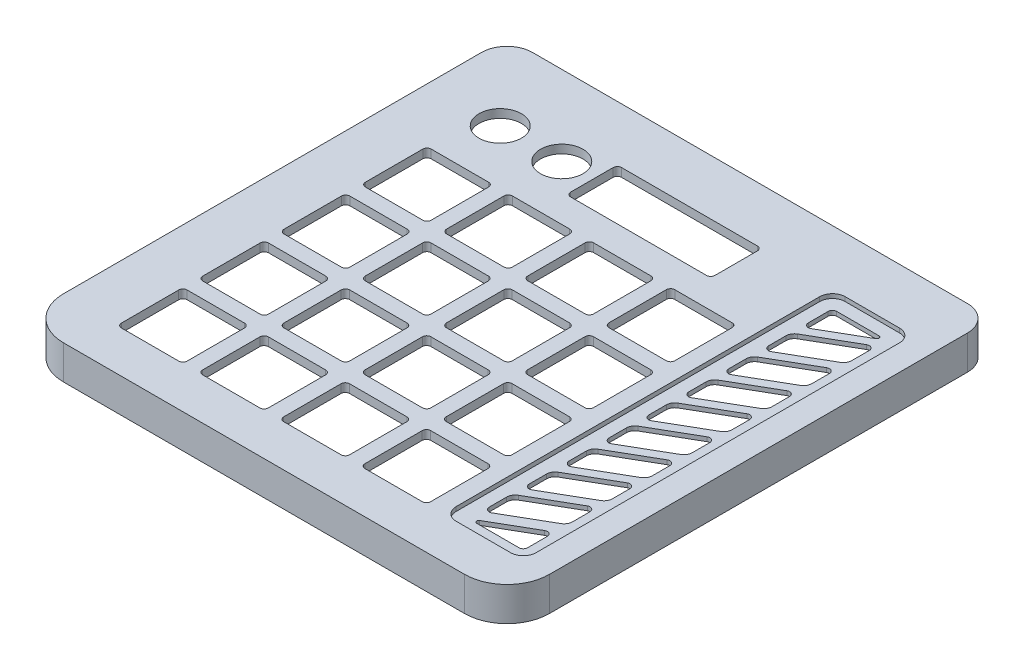
SolidWorks part; units mm, degrees
ref_plane "Plan de face" through (0, 0, 0) normal (0, 0, 1) x (1, 0, 0)
ref_plane "Plan de dessus" through (0, 0, 0) normal (0, 1, 0) x (1, 0, 0)
ref_plane "Plan de droite" through (0, 0, 0) normal (1, 0, 0) x (0, 0, -1)
sketch "Esquisse2" plane through (0, 0, 0) normal (0, 1, 0) x (1, 0, 0)
  line L1 (8, 0) -> (102.5, 0)
  line L2 (0, 8) -> (0, 106.5)
  line L3 (4, 110.5) -> (106.5, 110.5)
  line L4 (110.5, 8) -> (110.5, 106.5)
  line L5 (8, -2) -> (102.5, -2)
  line L6 (-2, 8) -> (-2, 106.5)
  line L7 (4, 112.5) -> (106.5, 112.5)
  line L8 (112.5, 8) -> (112.5, 106.5)
  arc A0 (0, 106.5) -> (4, 110.5) centre (4, 106.5) cw
  arc A1 (106.5, 110.5) -> (110.5, 106.5) centre (106.5, 106.5) cw
  arc A2 (102.5, 0) -> (110.5, 8) centre (102.5, 8) ccw
  arc A3 (8, 0) -> (0, 8) centre (8, 8) cw
  arc A4 (-2, 106.5) -> (4, 112.5) centre (4, 106.5) cw
  arc A5 (112.5, 106.5) -> (106.5, 112.5) centre (106.5, 106.5) ccw
  arc A6 (102.5, -2) -> (112.5, 8) centre (102.5, 8) ccw
  arc A7 (8, -2) -> (-2, 8) centre (8, 8) cw
  point P7 (0, 110.5)
  point P12 (110.5, 0)
  point P15 (0, 0)
  dimension "D3" = 4
  dimension "D4" = 8
  dimension "D9" = 6
  dimension "D10" = 6
  dimension "D11" = 10
  dimension "D1" = 110.5
  dimension "D2" = 110.5
  dimension "D5" = 2
  dimension "D6" = 2
  dimension "D7" = 2
  dimension "D8" = 2
extrude "Boss.-Extru.1" add sketch "Esquisse2" along normal blind 6
sketch "Esquisse3" plane through (0, 6, 0) normal (0, 1, 0) x (1, 0, 0)
  line L0 (-2, 106.5) -> (-2, 112.5) construction
  line L1 (4, 112.5) -> (-2, 112.5) construction
  line L2 (102.5, -2) -> (112.5, -2) construction
  line L3 (4, 112.5) -> (106.5, 112.5)
  line L4 (-2, 106.5) -> (-2, 8)
  line L5 (8, -2) -> (102.5, -2)
  line L6 (112.5, 106.5) -> (112.5, 8)
  line L7 (112.5, 8) -> (112.5, -2) construction
  arc A0 (106.5, 112.5) -> (112.5, 106.5) centre (106.5, 106.5) cw
  arc A1 (4, 112.5) -> (-2, 106.5) centre (4, 106.5) ccw
  arc A2 (102.5, -2) -> (112.5, 8) centre (102.5, 8) ccw
  arc A3 (-2, 8) -> (8, -2) centre (8, 8) ccw
  dimension "D1" = 6
  dimension "D2" = 10
extrude "Boss.-Extru.2" add sketch "Esquisse3" along normal blind 2
sketch "Esquisse5" plane through (0, 8, 0) normal (0, 1, 0) x (1, 0, 0)
  line L0 (112.5, 8) -> (112.5, 106.5) construction
  line L5 (-2, 106.5) -> (-2, 8) construction
  line L6 (38, 87.5) -> (70, 87.5)
  line L8 (11.8, 80.849) -> (25.3, 80.849)
  line L9 (10.8, 79.849) -> (10.8, 66.349)
  line L10 (11.8, 65.349) -> (25.3, 65.349)
  line L11 (26.3, 79.849) -> (26.3, 66.349)
  line L75 (29.9262, 79.849) -> (29.9262, 66.349)
  line L76 (30.9262, 80.849) -> (44.4262, 80.849)
  line L77 (45.4262, 79.849) -> (45.4262, 66.349)
  line L78 (30.9262, 65.349) -> (44.4262, 65.349)
  line L79 (49.0524, 79.849) -> (49.0524, 66.349)
  line L80 (50.0524, 80.849) -> (63.5524, 80.849)
  line L81 (64.5524, 79.849) -> (64.5524, 66.349)
  line L82 (50.0524, 65.349) -> (63.5524, 65.349)
  line L83 (68.1786, 79.849) -> (68.1786, 66.349)
  line L84 (69.1786, 80.849) -> (82.6786, 80.849)
  line L85 (83.6786, 79.849) -> (83.6786, 66.349)
  line L86 (69.1786, 65.349) -> (82.6786, 65.349)
  line L87 (29.9262, 60.6815) -> (29.9262, 47.1815)
  line L88 (30.9262, 61.6815) -> (44.4262, 61.6815)
  line L89 (45.4262, 60.6815) -> (45.4262, 47.1815)
  line L90 (30.9262, 46.1815) -> (44.4262, 46.1815)
  line L91 (49.0524, 60.6815) -> (49.0524, 47.1815)
  line L92 (50.0524, 61.6815) -> (63.5524, 61.6815)
  line L93 (64.5524, 60.6815) -> (64.5524, 47.1815)
  line L94 (50.0524, 46.1815) -> (63.5524, 46.1815)
  line L95 (68.1786, 60.6815) -> (68.1786, 47.1815)
  line L96 (69.1786, 61.6815) -> (82.6786, 61.6815)
  line L97 (83.6786, 60.6815) -> (83.6786, 47.1815)
  line L98 (69.1786, 46.1815) -> (82.6786, 46.1815)
  line L99 (29.9262, 41.514) -> (29.9262, 28.014)
  line L100 (30.9262, 42.514) -> (44.4262, 42.514)
  line L101 (45.4262, 41.514) -> (45.4262, 28.014)
  line L102 (30.9262, 27.014) -> (44.4262, 27.014)
  line L103 (49.0524, 41.514) -> (49.0524, 28.014)
  line L104 (50.0524, 42.514) -> (63.5524, 42.514)
  line L105 (64.5524, 41.514) -> (64.5524, 28.014)
  line L106 (50.0524, 27.014) -> (63.5524, 27.014)
  line L107 (68.1786, 41.514) -> (68.1786, 28.014)
  line L108 (69.1786, 42.514) -> (82.6786, 42.514)
  line L109 (83.6786, 41.514) -> (83.6786, 28.014)
  line L110 (69.1786, 27.014) -> (82.6786, 27.014)
  line L111 (29.9262, 22.3465) -> (29.9262, 8.8465)
  line L112 (30.9262, 23.3465) -> (44.4262, 23.3465)
  line L113 (45.4262, 22.3465) -> (45.4262, 8.8465)
  line L114 (30.9262, 7.8465) -> (44.4262, 7.8465)
  line L115 (49.0524, 22.3465) -> (49.0524, 8.8465)
  line L116 (50.0524, 23.3465) -> (63.5524, 23.3465)
  line L117 (64.5524, 22.3465) -> (64.5524, 8.8465)
  line L118 (50.0524, 7.8465) -> (63.5524, 7.8465)
  line L119 (68.1786, 22.3465) -> (68.1786, 8.8465)
  line L120 (69.1786, 23.3465) -> (82.6786, 23.3465)
  line L121 (83.6786, 22.3465) -> (83.6786, 8.8465)
  line L122 (69.1786, 7.8465) -> (82.6786, 7.8465)
  line L123 (10.8, 60.6815) -> (10.8, 47.1815)
  line L124 (11.8, 61.6815) -> (25.3, 61.6815)
  line L125 (26.3, 60.6815) -> (26.3, 47.1815)
  line L126 (11.8, 46.1815) -> (25.3, 46.1815)
  line L127 (10.8, 41.514) -> (10.8, 28.014)
  line L128 (11.8, 42.514) -> (25.3, 42.514)
  line L129 (26.3, 41.514) -> (26.3, 28.014)
  line L130 (11.8, 27.014) -> (25.3, 27.014)
  line L131 (10.8, 22.3465) -> (10.8, 8.8465)
  line L132 (11.8, 23.3465) -> (25.3, 23.3465)
  line L133 (26.3, 22.3465) -> (26.3, 8.8465)
  line L134 (11.8, 7.8465) -> (25.3, 7.8465)
  line L135 (106.5, 112.5) -> (4, 112.5) construction
  line L136 (37, 88.5) -> (37, 98.5)
  line L137 (38, 99.5) -> (70, 99.5)
  line L138 (71, 88.5) -> (71, 98.5)
  arc A0 (25.3, 65.349) -> (26.3, 66.349) centre (25.3, 66.349) ccw
  arc A1 (10.8, 66.349) -> (11.8, 65.349) centre (11.8, 66.349) ccw
  arc A2 (11.8, 80.849) -> (10.8, 79.849) centre (11.8, 79.849) ccw
  arc A3 (25.3, 80.849) -> (26.3, 79.849) centre (25.3, 79.849) cw
  arc A4 (30.9262, 80.849) -> (29.9262, 79.849) centre (30.9262, 79.849) ccw
  arc A5 (29.9262, 66.349) -> (30.9262, 65.349) centre (30.9262, 66.349) ccw
  arc A6 (44.4262, 80.849) -> (45.4262, 79.849) centre (44.4262, 79.849) cw
  arc A7 (44.4262, 65.349) -> (45.4262, 66.349) centre (44.4262, 66.349) ccw
  arc A8 (50.0524, 80.849) -> (49.0524, 79.849) centre (50.0524, 79.849) ccw
  arc A9 (49.0524, 66.349) -> (50.0524, 65.349) centre (50.0524, 66.349) ccw
  arc A10 (63.5524, 80.849) -> (64.5524, 79.849) centre (63.5524, 79.849) cw
  arc A11 (63.5524, 65.349) -> (64.5524, 66.349) centre (63.5524, 66.349) ccw
  arc A12 (69.1786, 80.849) -> (68.1786, 79.849) centre (69.1786, 79.849) ccw
  arc A13 (68.1786, 66.349) -> (69.1786, 65.349) centre (69.1786, 66.349) ccw
  arc A14 (82.6786, 80.849) -> (83.6786, 79.849) centre (82.6786, 79.849) cw
  arc A15 (82.6786, 65.349) -> (83.6786, 66.349) centre (82.6786, 66.349) ccw
  arc A16 (30.9262, 61.6815) -> (29.9262, 60.6815) centre (30.9262, 60.6815) ccw
  arc A17 (29.9262, 47.1815) -> (30.9262, 46.1815) centre (30.9262, 47.1815) ccw
  arc A18 (44.4262, 61.6815) -> (45.4262, 60.6815) centre (44.4262, 60.6815) cw
  arc A19 (44.4262, 46.1815) -> (45.4262, 47.1815) centre (44.4262, 47.1815) ccw
  arc A20 (50.0524, 61.6815) -> (49.0524, 60.6815) centre (50.0524, 60.6815) ccw
  arc A21 (49.0524, 47.1815) -> (50.0524, 46.1815) centre (50.0524, 47.1815) ccw
  arc A22 (63.5524, 61.6815) -> (64.5524, 60.6815) centre (63.5524, 60.6815) cw
  arc A23 (63.5524, 46.1815) -> (64.5524, 47.1815) centre (63.5524, 47.1815) ccw
  arc A24 (69.1786, 61.6815) -> (68.1786, 60.6815) centre (69.1786, 60.6815) ccw
  arc A25 (68.1786, 47.1815) -> (69.1786, 46.1815) centre (69.1786, 47.1815) ccw
  arc A26 (82.6786, 61.6815) -> (83.6786, 60.6815) centre (82.6786, 60.6815) cw
  arc A27 (82.6786, 46.1815) -> (83.6786, 47.1815) centre (82.6786, 47.1815) ccw
  arc A28 (30.9262, 42.514) -> (29.9262, 41.514) centre (30.9262, 41.514) ccw
  arc A29 (29.9262, 28.014) -> (30.9262, 27.014) centre (30.9262, 28.014) ccw
  arc A30 (44.4262, 42.514) -> (45.4262, 41.514) centre (44.4262, 41.514) cw
  arc A31 (44.4262, 27.014) -> (45.4262, 28.014) centre (44.4262, 28.014) ccw
  arc A32 (50.0524, 42.514) -> (49.0524, 41.514) centre (50.0524, 41.514) ccw
  arc A33 (49.0524, 28.014) -> (50.0524, 27.014) centre (50.0524, 28.014) ccw
  arc A34 (63.5524, 42.514) -> (64.5524, 41.514) centre (63.5524, 41.514) cw
  arc A35 (63.5524, 27.014) -> (64.5524, 28.014) centre (63.5524, 28.014) ccw
  arc A36 (69.1786, 42.514) -> (68.1786, 41.514) centre (69.1786, 41.514) ccw
  arc A37 (68.1786, 28.014) -> (69.1786, 27.014) centre (69.1786, 28.014) ccw
  arc A38 (82.6786, 42.514) -> (83.6786, 41.514) centre (82.6786, 41.514) cw
  arc A39 (82.6786, 27.014) -> (83.6786, 28.014) centre (82.6786, 28.014) ccw
  arc A40 (30.9262, 23.3465) -> (29.9262, 22.3465) centre (30.9262, 22.3465) ccw
  arc A41 (29.9262, 8.8465) -> (30.9262, 7.8465) centre (30.9262, 8.8465) ccw
  arc A42 (44.4262, 23.3465) -> (45.4262, 22.3465) centre (44.4262, 22.3465) cw
  arc A43 (44.4262, 7.8465) -> (45.4262, 8.8465) centre (44.4262, 8.8465) ccw
  arc A44 (50.0524, 23.3465) -> (49.0524, 22.3465) centre (50.0524, 22.3465) ccw
  arc A45 (49.0524, 8.8465) -> (50.0524, 7.8465) centre (50.0524, 8.8465) ccw
  arc A46 (63.5524, 23.3465) -> (64.5524, 22.3465) centre (63.5524, 22.3465) cw
  arc A47 (63.5524, 7.8465) -> (64.5524, 8.8465) centre (63.5524, 8.8465) ccw
  arc A48 (69.1786, 23.3465) -> (68.1786, 22.3465) centre (69.1786, 22.3465) ccw
  arc A49 (68.1786, 8.8465) -> (69.1786, 7.8465) centre (69.1786, 8.8465) ccw
  arc A50 (82.6786, 23.3465) -> (83.6786, 22.3465) centre (82.6786, 22.3465) cw
  arc A51 (82.6786, 7.8465) -> (83.6786, 8.8465) centre (82.6786, 8.8465) ccw
  arc A52 (11.8, 61.6815) -> (10.8, 60.6815) centre (11.8, 60.6815) ccw
  arc A53 (10.8, 47.1815) -> (11.8, 46.1815) centre (11.8, 47.1815) ccw
  arc A54 (25.3, 61.6815) -> (26.3, 60.6815) centre (25.3, 60.6815) cw
  arc A55 (25.3, 46.1815) -> (26.3, 47.1815) centre (25.3, 47.1815) ccw
  arc A56 (11.8, 42.514) -> (10.8, 41.514) centre (11.8, 41.514) ccw
  arc A57 (10.8, 28.014) -> (11.8, 27.014) centre (11.8, 28.014) ccw
  arc A58 (25.3, 42.514) -> (26.3, 41.514) centre (25.3, 41.514) cw
  arc A59 (25.3, 27.014) -> (26.3, 28.014) centre (25.3, 28.014) ccw
  arc A60 (11.8, 23.3465) -> (10.8, 22.3465) centre (11.8, 22.3465) ccw
  arc A61 (10.8, 8.8465) -> (11.8, 7.8465) centre (11.8, 8.8465) ccw
  arc A62 (25.3, 23.3465) -> (26.3, 22.3465) centre (25.3, 22.3465) cw
  arc A63 (25.3, 7.8465) -> (26.3, 8.8465) centre (25.3, 8.8465) ccw
  arc A66 (38, 87.5) -> (37, 88.5) centre (38, 88.5) cw
  arc A67 (70, 87.5) -> (71, 88.5) centre (70, 88.5) ccw
  arc A68 (70, 99.5) -> (71, 98.5) centre (70, 98.5) cw
  arc A69 (37, 98.5) -> (38, 99.5) centre (38, 98.5) cw
  circle A70 centre (29.7, 93.7) radius 5
  circle A71 centre (15.2, 93.7) radius 5
  point P82 (10.8, 65.349)
  point P85 (10.8, 80.849)
  point P88 (26.3, 80.849)
  dimension "D10" = 1
  dimension "D11" = 18.8
  dimension "D12" = 18.8
  dimension "D17" = 1
  dimension "D15" = 10
  dimension "D16" = 10
  dimension "D2" = 3.6262
  dimension "D3" = 3.6675
  dimension "D4" = 31.651
  dimension "D5" = 12.8
  dimension "D6" = 15.5
  dimension "D7" = 15.5
  dimension "D8" = 4
  dimension "D13" = 17.2
  dimension "D14" = 14.5
  dimension "D18" = 13
  dimension "D19" = 41.5
  dimension "D20" = 34
  dimension "D21" = 12
  dimension "D9" = 4
extrude "Enlèv. mat.-Extru.1" cut sketch "Esquisse5" against normal blind 33 contours A3 L8 A2 L9 A1 L10 A0 L11 | L78 A7 L77 A6 L76 A4 L75 A5 | L82 A11 L81 A10 L80 A8 L79 A9 | L86 A15 L85 A14 L84 A12 L83 A13 | L98 A27 L97 A26 L96 A24 L95 A25 | L94 A23 L93 A22 L92 A20 L91 A21 | L90 A19 L89 A18 L88 A16 L87 A17 | L126 A55 L125 A54 L124 A52 L123 A53 | L130 A59 L129 A58 L128 A56 L127 A57 | L102 A31 L101 A30 L100 A28 L99 A29 | L106 A35 L105 A34 L104 A32 L103 A33 | L110 A39 L109 A38 L108 A36 L107 A37 | L122 A51 L121 A50 L120 A48 L119 A49 | L118 A47 L117 A46 L116 A44 L115 A45 | L114 A43 L113 A42 L112 A40 L111 A41 | L134 A63 L133 A62 L132 A60 L131 A61 | A69 L137 A68 L138 A67 L6 A66 L136 | A71 | A70 region at (18.55, 8, -73.099) region at (37.6762, 8, -73.099) region at (56.8024, 8, -73.099) region at (75.9286, 8, -73.099) region at (37.6762, 8, -53.9315) region at (56.8024, 8, -53.9315) region at (75.9286, 8, -53.9315) region at (37.6762, 8, -34.764) region at (56.8024, 8, -34.764) region at (75.9286, 8, -34.764) region at (37.6762, 8, -15.5965) region at (56.8024, 8, -15.5965) region at (75.9286, 8, -15.5965) region at (18.55, 8, -53.9315) region at (18.55, 8, -34.764) region at (18.55, 8, -15.5965)
sketch "Esquisse6" plane through (0, 8, 0) normal (0, 1, 0) x (1, 0, 0)
  line L0 (83.6786, 79.849) -> (83.6786, 66.349) construction
  line L1 (90.6786, 99.5) -> (103.5, 99.5)
  line L2 (87.6786, 96.5) -> (87.6786, 10.8465)
  line L3 (90.6786, 7.8465) -> (103.5, 7.8465)
  line L4 (106.5, 96.5) -> (106.5, 10.8465)
  line L5 (112.5, 8) -> (112.5, 106.5) construction
  line L6 (91.6786, 87.2749) -> (102, 93.234)
  line L7 (103.5, 92.3679) -> (103.5, 88.2547)
  line L8 (102.5, 86.5226) -> (92.1786, 80.5636)
  line L9 (69.1786, 7.8465) -> (82.6786, 7.8465) construction
  line L10 (38, 99.5) -> (70, 99.5) construction
  line L11 (90.6786, 95.5) -> (90.6786, 90.8296)
  line L12 (92.1786, 89.9636) -> (101.884, 95.567)
  line L13 (101.634, 96.5) -> (91.6786, 96.5)
  line L14 (102.5, 10.8465) -> (92.5446, 10.8465)
  line L15 (92.2946, 11.7795) -> (102, 17.3829)
  line L16 (103.5, 16.5169) -> (103.5, 11.8465)
  line L17 (90.6786, 96.5) -> (90.6786, 10.8465) construction
  line L18 (103.5, 10.8465) -> (103.5, 96.5) construction
  line L19 (90.6786, 81.4296) -> (90.6786, 85.5429)
  line L20 (90.6786, 72.0296) -> (90.6786, 76.1429)
  line L21 (91.6786, 77.8749) -> (102, 83.834)
  line L22 (103.5, 82.9679) -> (103.5, 78.8547)
  line L23 (102.5, 77.1226) -> (92.1786, 71.1636)
  line L24 (90.6786, 62.6296) -> (90.6786, 66.7429)
  line L25 (91.6786, 68.4749) -> (102, 74.434)
  line L26 (103.5, 73.5679) -> (103.5, 69.4547)
  line L27 (102.5, 67.7226) -> (92.1786, 61.7636)
  line L28 (90.6786, 53.2296) -> (90.6786, 57.3429)
  line L29 (91.6786, 59.0749) -> (102, 65.034)
  line L30 (103.5, 64.1679) -> (103.5, 60.0547)
  line L31 (102.5, 58.3226) -> (92.1786, 52.3636)
  line L32 (90.6786, 43.8296) -> (90.6786, 47.9429)
  line L33 (91.6786, 49.6749) -> (102, 55.634)
  line L34 (103.5, 54.7679) -> (103.5, 50.6547)
  line L35 (102.5, 48.9226) -> (92.1786, 42.9636)
  line L36 (90.6786, 34.4296) -> (90.6786, 38.5429)
  line L37 (91.6786, 40.2749) -> (102, 46.234)
  line L38 (103.5, 45.3679) -> (103.5, 41.2547)
  line L39 (102.5, 39.5226) -> (92.1786, 33.5636)
  line L40 (90.6786, 25.0296) -> (90.6786, 29.1429)
  line L41 (91.6786, 30.8749) -> (102, 36.834)
  line L42 (103.5, 35.9679) -> (103.5, 31.8547)
  line L43 (102.5, 30.1226) -> (92.1786, 24.1636)
  line L44 (90.6786, 15.6296) -> (90.6786, 19.7429)
  line L45 (91.6786, 21.4749) -> (102, 27.434)
  line L46 (103.5, 26.5679) -> (103.5, 22.4547)
  line L47 (102.5, 20.7226) -> (92.1786, 14.7636)
  arc A0 (103.5, 7.8465) -> (106.5, 10.8465) centre (103.5, 10.8465) ccw
  arc A1 (87.6786, 10.8465) -> (90.6786, 7.8465) centre (90.6786, 10.8465) ccw
  arc A2 (103.5, 99.5) -> (106.5, 96.5) centre (103.5, 96.5) cw
  arc A3 (90.6786, 99.5) -> (87.6786, 96.5) centre (90.6786, 96.5) ccw
  arc A4 (102, 27.434) -> (103.5, 26.5679) centre (102.5, 26.5679) cw
  arc A5 (90.6786, 15.6296) -> (92.1786, 14.7636) centre (91.6786, 15.6296) ccw
  arc A6 (90.6786, 25.0296) -> (92.1786, 24.1636) centre (91.6786, 25.0296) ccw
  arc A7 (102, 36.834) -> (103.5, 35.9679) centre (102.5, 35.9679) cw
  arc A8 (90.6786, 34.4296) -> (92.1786, 33.5636) centre (91.6786, 34.4296) ccw
  arc A9 (102, 46.234) -> (103.5, 45.3679) centre (102.5, 45.3679) cw
  arc A10 (102, 55.634) -> (103.5, 54.7679) centre (102.5, 54.7679) cw
  arc A11 (90.6786, 43.8296) -> (92.1786, 42.9636) centre (91.6786, 43.8296) ccw
  arc A12 (90.6786, 53.2296) -> (92.1786, 52.3636) centre (91.6786, 53.2296) ccw
  arc A13 (102, 65.034) -> (103.5, 64.1679) centre (102.5, 64.1679) cw
  arc A14 (90.6786, 62.6296) -> (92.1786, 61.7636) centre (91.6786, 62.6296) ccw
  arc A15 (102, 74.434) -> (103.5, 73.5679) centre (102.5, 73.5679) cw
  arc A16 (102, 83.834) -> (103.5, 82.9679) centre (102.5, 82.9679) cw
  arc A17 (90.6786, 72.0296) -> (92.1786, 71.1636) centre (91.6786, 72.0296) ccw
  arc A18 (92.1786, 80.5636) -> (90.6786, 81.4296) centre (91.6786, 81.4296) cw
  arc A19 (102, 93.234) -> (103.5, 92.3679) centre (102.5, 92.3679) cw
  arc A20 (90.6786, 19.7429) -> (91.6786, 21.4749) centre (92.6786, 19.7429) cw
  arc A21 (103.5, 22.4547) -> (102.5, 20.7226) centre (101.5, 22.4547) cw
  arc A22 (103.5, 31.8547) -> (102.5, 30.1226) centre (101.5, 31.8547) cw
  arc A23 (90.6786, 29.1429) -> (91.6786, 30.8749) centre (92.6786, 29.1429) cw
  arc A24 (103.5, 41.2547) -> (102.5, 39.5226) centre (101.5, 41.2547) cw
  arc A25 (90.6786, 38.5429) -> (91.6786, 40.2749) centre (92.6786, 38.5429) cw
  arc A26 (103.5, 50.6547) -> (102.5, 48.9226) centre (101.5, 50.6547) cw
  arc A27 (90.6786, 47.9429) -> (91.6786, 49.6749) centre (92.6786, 47.9429) cw
  arc A28 (103.5, 60.0547) -> (102.5, 58.3226) centre (101.5, 60.0547) cw
  arc A29 (90.6786, 57.3429) -> (91.6786, 59.0749) centre (92.6786, 57.3429) cw
  arc A30 (103.5, 88.2547) -> (102.5, 86.5226) centre (101.5, 88.2547) cw
  arc A31 (91.6786, 87.2749) -> (90.6786, 85.5429) centre (92.6786, 85.5429) ccw
  arc A32 (103.5, 78.8547) -> (102.5, 77.1226) centre (101.5, 78.8547) cw
  arc A33 (90.6786, 76.1429) -> (91.6786, 77.8749) centre (92.6786, 76.1429) cw
  arc A34 (90.6786, 66.7429) -> (91.6786, 68.4749) centre (92.6786, 66.7429) cw
  arc A35 (103.5, 69.4547) -> (102.5, 67.7226) centre (101.5, 69.4547) cw
  arc A36 (101.884, 95.567) -> (101.634, 96.5) centre (101.634, 96) ccw
  arc A37 (92.5446, 10.8465) -> (92.2946, 11.7795) centre (92.5446, 11.3465) cw
  arc A38 (102.5, 10.8465) -> (103.5, 11.8465) centre (102.5, 11.8465) ccw
  arc A39 (102, 17.3829) -> (103.5, 16.5169) centre (102.5, 16.5169) cw
  arc A40 (90.6786, 90.8296) -> (92.1786, 89.9636) centre (91.6786, 90.8296) ccw
  arc A41 (90.6786, 95.5) -> (91.6786, 96.5) centre (91.6786, 95.5) cw
  point P84 (90.6786, 79.6976)
  point P87 (103.5, 94.1)
  point P110 (103.5, 87.1)
  point P113 (90.6786, 86.6976)
  point P135 (90.6786, 89.0976)
  dimension "D3" = 3
  dimension "D11" = 1
  dimension "D12" = 2
  dimension "D13" = 0.5
  dimension "D14" = 1
  dimension "D1" = 4
  dimension "D2" = 6
  dimension "D4" = 30
  dimension "D5" = 30
  dimension "D6" = 2.4
  dimension "D7" = 2.4
  dimension "D8" = 7
  dimension "D9" = 8
  dimension "D10" = 2.0785
extrude "Enlèv. mat.-Extru.2" cut sketch "Esquisse6" against normal blind 2 contours L12 L13 L11 | L23 L22 L21 L20 | L27 L26 L25 L24 | L31 L30 L29 L28 | L35 L34 L33 L32 | L39 L38 L37 L36 | L43 L42 L41 L40 | L47 L46 L45 L44 | L16 L15 L14 | L19 A31 L6 A19 L7 A30 L8 A18 region at (94.9297, 8, -94.057) region at (99.2489, 8, -13.2895) region at (97.0893, 8, -77.4988) region at (97.0893, 8, -68.0988) region at (97.0893, 8, -58.6988) region at (97.0893, 8, -49.2988) region at (97.0893, 8, -39.8988) region at (97.0893, 8, -30.4988) region at (97.0893, 8, -21.0988)
extrude "Enlèv. mat.-Extru.3" cut sketch "Esquisse6<3>" against normal blind 1
sketch "Esquisse6<3>" plane through (0, 8, 0) normal (0, 1, 0) x (1, 0, 0) same geometry as "Esquisse6"
sketch "Esquisse10" plane through (0, 0, -112.5) normal (0, 0, -1) x (-1, 0, 0)
  line L0 (-106.5, 0) -> (-4, 0) construction
  line L1 (-99.75, 0) -> (-83.75, 0)
  line L2 (-99.75, 0) -> (-99.75, 2)
  line L3 (-97.75, 4) -> (-85.75, 4)
  line L4 (-83.75, 0) -> (-83.75, 2)
  line L5 (-112.5, 8) -> (-112.5, 0) construction
  arc A0 (-85.75, 4) -> (-83.75, 2) centre (-85.75, 2) cw
  arc A1 (-99.75, 2) -> (-97.75, 4) centre (-97.75, 2) cw
  point P10 (-83.75, 4)
  point P13 (-99.75, 4)
  dimension "D4" = 2
  dimension "D1" = 12.75
  dimension "D2" = 16
  dimension "D3" = 4
extrude "Enlèv. mat.-Extru.5" cut sketch "Esquisse10" against normal blind 2
